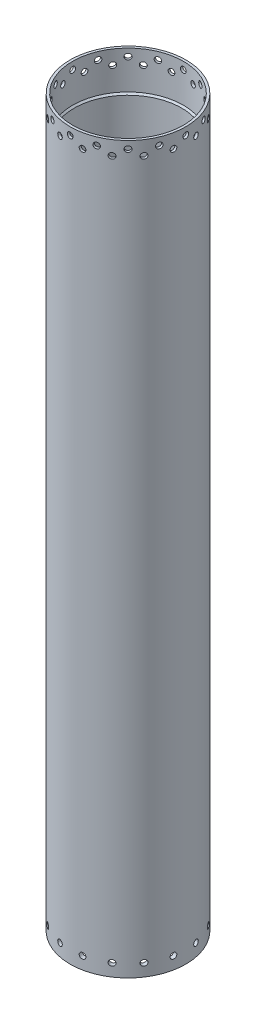
SolidWorks part; units mm, degrees
material "Stop 6061"
ref_plane "Płaszczyzna przednia" through (0, 0, 0) normal (0, 0, 1) x (1, 0, 0)
ref_plane "Płaszczyzna górna" through (0, 0, 0) normal (0, 1, 0) x (1, 0, 0)
ref_plane "Płaszczyzna prawa" through (0, 0, 0) normal (1, 0, 0) x (0, 0, -1)
sketch "Szkic1" plane through (0, 0, 0) normal (0, 0, 1) x (1, 0, 0)
  line L0 (0, 552.4394) -> (0, -579.7933) construction
  line L1 (70, -438.5) -> (70, 438.5)
  line L2 (70, 438.5) -> (67, 438.5)
  line L3 (67, 438.5) -> (67, 390.5)
  line L4 (67, 390.5) -> (65, 390.5)
  line L5 (65, 390.5) -> (65, -438.5)
  line L6 (65, -438.5) -> (70, -438.5)
  point P10 (70, 0)
  dimension "D1" = 877
  dimension "D2" = 5
  dimension "D3" = 48
  dimension "D4" = 3
  dimension "D5" = 65
revolve "Obrót1" add sketch "Szkic1" angle 360 about L0
chamfer "Sfazowanie1" distance 2 angle 45 1 edges at (0, 390.5, 67)
ref_plane "Płaszczyzna1" through (0, 0, 70) normal (0, 0, 1) x (1, 0, 0)
sketch "Szkic4" plane through (0, 0, 70) normal (0, 0, 1) x (1, 0, 0)
  line L0 (0, 438.5) -> (0, -438.5) construction
  line L1 (70, 438.5) -> (-70, 438.5) construction
  line L2 (-70, -438.5) -> (70, -438.5) construction
  circle A0 centre (0, 429.5) radius 3.5
  dimension "9" = 9
ref_plane "Płaszczyzna2" through (-13.6563, 0, 68.655) normal (-0.1951, 0, 0.9808) x (0, 1, 0)
sketch "Szkic6" plane through (-13.6563, 0, 68.655) normal (-0.1951, 0, 0.9808) x (0, 1, 0)
  line L0 (438.5, 0) -> (-438.5, 0) construction
  line L1 (438.5, -70) -> (438.5, 70) construction
  line L2 (-438.5, 70) -> (-438.5, -70) construction
  circle A0 centre (421.5, 0) radius 3.5
  dimension "D1" = 17
extrude "Wytnij-wyciągnięcie2" cut sketch "Szkic6" against normal blind 10
pattern_circular "Szyk kołowy2" count 16 over 360 about axis through (0, 552.4394, 0) along (0, 1, 0) of "Wytnij-wyciągnięcie2" reverse direction yes
extrude "Wytnij-wyciągnięcie4" cut sketch "Szkic4" against normal blind 10
pattern_circular "Szyk kołowy3" count 16 over 360 about axis through (0, 552.4394, 0) along (0, 1, 0) of "Wytnij-wyciągnięcie4" reverse direction yes
sketch "Szkic7" plane through (-13.6563, 0, 68.655) normal (-0.1951, 0, 0.9808) x (0, 1, 0)
  line L0 (438.5, 0) -> (-438.5, 0) construction
  line L1 (-438.5, 70) -> (-438.5, -70) construction
  line L2 (438.5, -70) -> (438.5, 70) construction
  circle A0 centre (-423.5, 0) radius 3.5
  dimension "D1" = 15
extrude "Wytnij-wyciągnięcie5" cut sketch "Szkic7" against normal blind 10
pattern_circular "Szyk kołowy4" count 16 over 360 about axis through (0, 552.4394, 0) along (0, 1, 0) of "Wytnij-wyciągnięcie5"
ref_plane "Płaszczyzna3" through (-58.2029, 0, -38.8899) normal (-0.8315, 0, -0.5556) x (0, 1, 0)
sketch "Szkic11" plane through (-58.2029, 0, -38.8899) normal (-0.8315, 0, -0.5556) x (0, 1, 0)
  line L0 (438.5, 0) -> (-438.5, 0) construction
  line L1 (-438.5, 70) -> (-438.5, -70) construction
  line L2 (438.5, -70) -> (438.5, 70) construction
  circle A0 centre (-423.5, 0) radius 2.05
  dimension "D1" = 15
  dimension "D2" = 4.1
